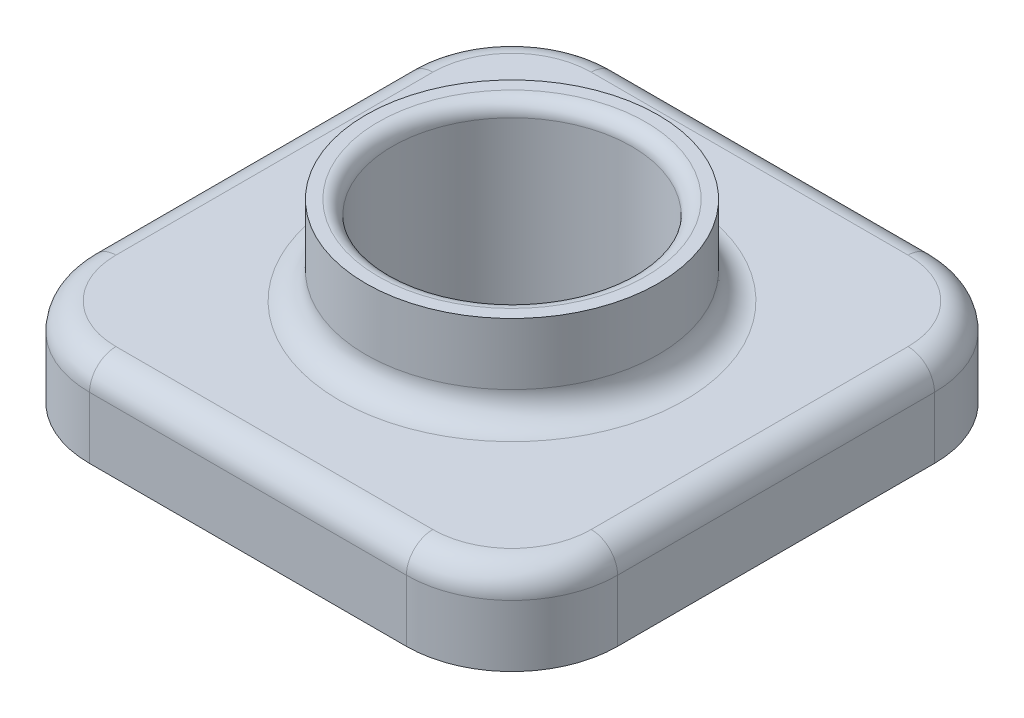
SolidWorks part; units mm, degrees
ref_plane "Front Plane" through (0, 0, 0) normal (0, 0, 1) x (1, 0, 0)
ref_plane "Top Plane" through (0, 0, 0) normal (0, 1, 0) x (1, 0, 0)
ref_plane "Right Plane" through (0, 0, 0) normal (1, 0, 0) x (0, 0, -1)
sketch "Sketch1" plane through (0, 0, 0) normal (0, 1, 0) x (1, 0, 0)
  circle A0 centre (0, 0) radius 6.8
  circle A1 centre (0, 0) radius 8.3
  dimension "D1" = 13.6
  dimension "D2" = 1.5
extrude "Boss-Extrude1" add sketch "Sketch1" along normal blind 5
sketch "Sketch2" plane through (0, 0, 0) normal (0, -1, 0) x (1, 0, 0)
  line L1 (-9, -15) -> (9, -15)
  line L2 (-15, -9) -> (-15, 9)
  line L3 (-9, 15) -> (9, 15)
  line L4 (15, -9) -> (15, 9)
  line L5 (-15, -15) -> (15, 15) construction
  line L6 (-15, 15) -> (15, -15) construction
  circle A0 centre (0, 0) radius 6.8
  arc A1 (-9, -15) -> (-15, -9) centre (-9, -9) cw
  arc A2 (9, -15) -> (15, -9) centre (9, -9) ccw
  arc A3 (9, 15) -> (15, 9) centre (9, 9) cw
  arc A4 (-15, 9) -> (-9, 15) centre (-9, 9) cw
  point P0 (0, 0)
  dimension "D3" = 6
  dimension "D1" = 30
  dimension "D2" = 30
extrude "Boss-Extrude2" add sketch "Sketch2" along normal blind 5
fillet "Fillet1" radius 0.8 1 edges at (0, 5, 6.8)
fillet "Fillet2" radius 1.5 9 edges at (0, 0, -15) (13.2426, 0, -13.2426) (15, 0, 0) (13.2426, 0, 13.2426) (0, 0, 15) (-13.2426, 0, 13.2426) (-15, 0, 0) (-13.2426, 0, -13.2426) (0, 0, 8.3)
